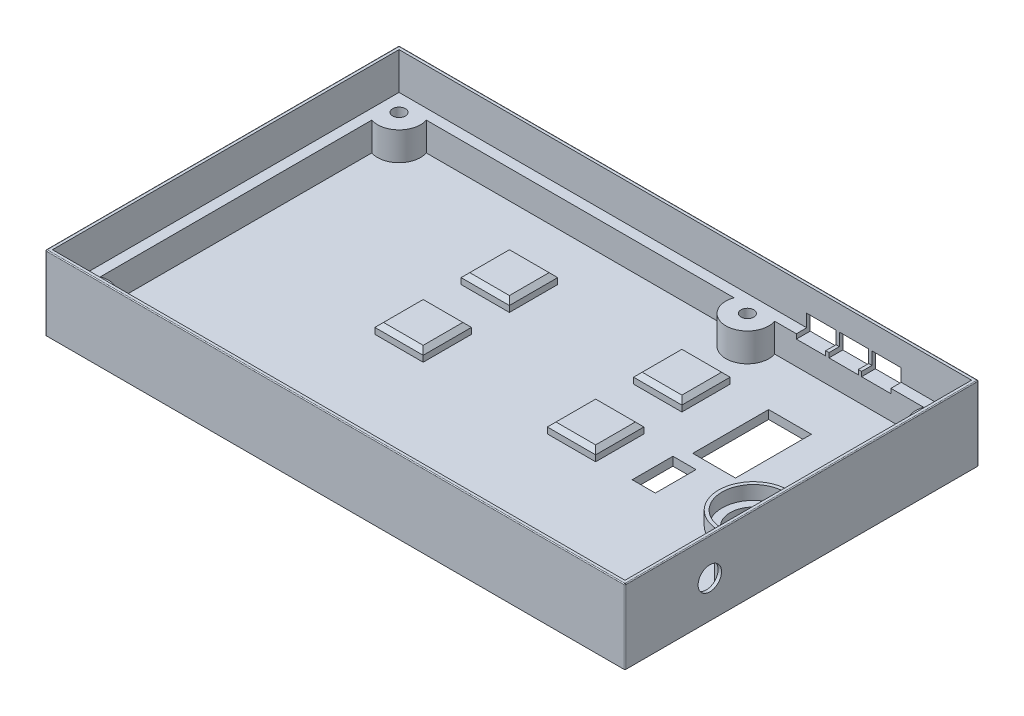
SolidWorks part; units mm, degrees
ref_plane "Front Plane" through (0, 0, 0) normal (0, 0, 1) x (1, 0, 0)
ref_plane "Top Plane" through (0, 0, 0) normal (0, 1, 0) x (1, 0, 0)
ref_plane "Right Plane" through (0, 0, 0) normal (1, 0, 0) x (0, 0, -1)
sketch "BaseSketch1" plane through (0, 0, 0) normal (0, 1, 0) x (1, 0, 0)
  line L1 (0, 0) -> (168, 0)
  line L2 (0, 0) -> (0, 102.5)
  line L3 (0, 102.5) -> (168, 102.5)
  line L4 (168, 0) -> (168, 102.5)
  line L5 (125.95, 83.7) -> (138.35, 83.7)
  line L6 (125.95, 83.7) -> (125.95, 61.7)
  line L7 (125.95, 61.7) -> (138.35, 61.7)
  line L8 (138.35, 83.7) -> (138.35, 61.7)
  line L9 (123.8, 46.3) -> (130.5, 46.3)
  line L10 (123.8, 46.3) -> (123.8, 58.1)
  line L11 (123.8, 58.1) -> (130.5, 58.1)
  line L12 (130.5, 46.3) -> (130.5, 58.1)
  circle A0 centre (57, 77.5) radius 2
  circle A1 centre (107, 77.5) radius 2
  circle A2 centre (57, 52.5) radius 2
  circle A3 centre (107, 52.5) radius 2
  circle A4 centre (6, 96.5) radius 1.85
  circle A5 centre (6, 6) radius 1.85
  circle A6 centre (162, 6) radius 1.85
  circle A7 centre (162, 96.5) radius 1.85
  circle A8 centre (107, 96.5) radius 1.85
  dimension "D16" = 3.7
  dimension "D7" = 4
  dimension "D1" = 102.5
  dimension "D2" = 168
  dimension "D3" = 50
  dimension "D4" = 25
  dimension "D6" = 25
  dimension "D8" = 22
  dimension "D9" = 12.4
  dimension "D10" = 40.8
  dimension "D12" = 6.7
  dimension "D13" = 11.8
  dimension "D15" = 56.2
  dimension "D17" = 6
  dimension "D18" = 6
  dimension "D19" = 6
  dimension "D20" = 6
  dimension "D5" = 57
  dimension "D11" = 42.05
  dimension "D14" = 44.2
  dimension "D21" = 107
extrude "BaseBoss-Extrude1" add sketch "BaseSketch1" along normal blind 2.5
sketch "Sketch2" plane through (0, 2.5, 0) normal (0, 1, 0) x (1, 0, 0)
  line L1 (0, 0) -> (168, 0)
  line L2 (0, 0) -> (0, 102.5)
  line L3 (0, 102.5) -> (168, 102.5)
  line L4 (168, 0) -> (168, 102.5)
  line L5 (4, 98.5) -> (164, 98.5)
  line L6 (4, 98.5) -> (4, 4)
  line L7 (4, 4) -> (164, 4)
  line L8 (164, 98.5) -> (164, 4)
  dimension "D1" = 4
  dimension "D2" = 4
  dimension "D3" = 4
  dimension "D4" = 4
extrude "WallBoss-Extrude2" add sketch "Sketch2" along normal blind 19
sketch "Sketch3" plane through (0, 2.5, 0) normal (0, 1, 0) x (1, 0, 0)
  line L1 (50, 84.5) -> (64, 84.5)
  line L2 (50, 84.5) -> (50, 70.5)
  line L3 (50, 70.5) -> (64, 70.5)
  line L4 (64, 84.5) -> (64, 70.5)
  line L5 (50, 84.5) -> (64, 70.5) construction
  line L6 (50, 70.5) -> (64, 84.5) construction
  line L7 (50, 59.5) -> (64, 59.5)
  line L8 (50, 59.5) -> (50, 45.5)
  line L9 (50, 45.5) -> (64, 45.5)
  line L10 (64, 59.5) -> (64, 45.5)
  line L11 (50, 59.5) -> (64, 45.5) construction
  line L12 (50, 45.5) -> (64, 59.5) construction
  line L13 (100, 84.5) -> (114, 84.5)
  line L14 (100, 84.5) -> (100, 70.5)
  line L15 (100, 70.5) -> (114, 70.5)
  line L16 (114, 84.5) -> (114, 70.5)
  line L17 (100, 84.5) -> (114, 70.5) construction
  line L18 (100, 70.5) -> (114, 84.5) construction
  line L19 (100, 59.5) -> (114, 59.5)
  line L20 (100, 59.5) -> (100, 45.5)
  line L21 (100, 45.5) -> (114, 45.5)
  line L22 (114, 59.5) -> (114, 45.5)
  line L23 (100, 59.5) -> (114, 45.5) construction
  line L24 (100, 45.5) -> (114, 59.5) construction
  point P0 (57, 77.5)
  point P6 (57, 52.5)
  point P12 (107, 77.5)
  point P18 (107, 52.5)
  dimension "D1" = 14
extrude "MountHoleBoss-Extrude3" add sketch "Sketch3" along normal blind 3
chamfer "MountHoleBossChamfer3" distance 1.25 angle 45 16 edges at (57, 5.5, -59.5) (107, 5.5, -59.5) (107, 5.5, -84.5) (57, 5.5, -84.5) (50, 5.5, -52.5) (100, 5.5, -52.5) (100, 5.5, -77.5) (50, 5.5, -77.5) (64, 5.5, -52.5) (114, 5.5, -52.5) (114, 5.5, -77.5) (64, 5.5, -77.5) (57, 5.5, -70.5) (57, 5.5, -45.5) (107, 5.5, -45.5) (107, 5.5, -70.5)
sketch "HDMI7MountHolesSketch8" plane through (0, 2.5, 0) normal (0, 1, 0) x (1, 0, 0)
  line L0 (164, 98.5) -> (4, 98.5) construction
  line L1 (4, 98.5) -> (4, 4) construction
  line L2 (4, 90.5986) -> (4, 98.5)
  line L3 (4, 98.5) -> (11.9014, 98.5)
  line L4 (164, 4) -> (164, 98.5) construction
  line L5 (4, 4) -> (164, 4) construction
  line L6 (4, 98.5) -> (4, 4) construction
  line L7 (4, 4) -> (164, 4) construction
  line L8 (156.0986, 98.5) -> (164, 98.5)
  line L9 (164, 98.5) -> (164, 90.5986)
  line L10 (156.0986, 4) -> (164, 4)
  line L11 (164, 4) -> (164, 11.9014)
  line L12 (11.9014, 4) -> (4, 4)
  line L13 (4, 4) -> (4, 11.9014)
  line L14 (101.0986, 98.5) -> (112.9014, 98.5)
  arc A0 (11.9014, 98.5) -> (4, 90.5986) centre (6, 96.5) cw
  circle A1 centre (6, 96.5) radius 1.85
  circle A2 centre (6, 96.5) radius 1.85 construction
  circle A3 centre (162, 96.5) radius 1.85
  circle A4 centre (162, 96.5) radius 1.85 construction
  arc A5 (164, 90.5986) -> (156.0986, 98.5) centre (162, 96.5) cw
  arc A6 (164, 11.9014) -> (156.0986, 4) centre (162, 6) ccw
  arc A7 (4, 11.9014) -> (11.9014, 4) centre (6, 6) cw
  circle A8 centre (162, 6) radius 1.85
  circle A9 centre (162, 6) radius 1.85 construction
  circle A10 centre (6, 6) radius 1.85
  circle A11 centre (6, 6) radius 1.85 construction
  arc A12 (101.0986, 98.5) -> (112.9014, 98.5) centre (107, 96.5) ccw
  circle A13 centre (107, 96.5) radius 1.85
  circle A14 centre (107, 96.5) radius 1.85 construction
extrude "HDMI7MountHolesBoss-Extrude4" add sketch "HDMI7MountHolesSketch8" along normal blind 8.25
sketch "DisplayButtonsSketch9" plane through (0, 0, -102.5) normal (0, 0, -1) x (-1, 0, 0)
  line L0 (-168, 21.5) -> (0, 21.5) construction
  line L1 (-146.6, 14.41) -> (-138.1, 14.41)
  line L2 (-146.6, 14.41) -> (-146.6, 9.41)
  line L3 (-146.6, 9.41) -> (-138.1, 9.41)
  line L4 (-138.1, 14.41) -> (-138.1, 9.41)
  line L5 (-137.15, 14.41) -> (-128.65, 14.41)
  line L6 (-137.15, 14.41) -> (-137.15, 9.41)
  line L7 (-137.15, 9.41) -> (-128.65, 9.41)
  line L8 (-128.65, 14.41) -> (-128.65, 9.41)
  line L9 (-127.7, 14.41) -> (-119.2, 14.41)
  line L10 (-127.7, 14.41) -> (-127.7, 9.41)
  line L11 (-127.7, 9.41) -> (-119.2, 9.41)
  line L12 (-119.2, 14.41) -> (-119.2, 9.41)
  line L13 (-168, 21.5) -> (-168, 0) construction
  dimension "D1" = 8.5
  dimension "D3" = 12.09
  dimension "D4" = 29.9
  dimension "D2" = 5
  dimension "D6" = 0.95
  dimension "D5" = 0.95
  dimension "D7" = 48.8
  dimension "D8" = 8.5
  dimension "D9" = 8.5
extrude "DisplayButtonsCut-Extrude1" cut sketch "DisplayButtonsSketch9" against normal up to next
sketch "AudioConnectorSketch10" plane through (168, 0, 0) normal (1, 0, 0) x (0, 0, -1)
  line L0 (0, 21.5) -> (102.5, 21.5) construction
  line L1 (0, 21.5) -> (0, 0) construction
  circle A0 centre (24.6, 10.7) radius 3.4
  dimension "D1" = 6.8
  dimension "D2" = 10.8
  dimension "D3" = 24.6
extrude "AudioConnectorCut-Extrude2" cut sketch "AudioConnectorSketch10" against normal up to next
sketch "M3BoreSketch11" plane through (0, 0, 0) normal (0, -1, 0) x (1, 0, 0)
  circle A0 centre (6, -6) radius 2.85
  circle A1 centre (162, -6) radius 2.85
  circle A2 centre (162, -96.5) radius 2.85
  circle A3 centre (6, -96.5) radius 2.85
  circle A4 centre (107, -96.5) radius 2.85
  dimension "D1" = 5.7
extrude "M3BoreCut-Extrude3" cut sketch "M3BoreSketch11" against normal blind 3
sketch "UpperThinWallSketch4" plane through (0, 21.5, 0) normal (0, 1, 0) x (1, 0, 0)
  line L1 (4, 98.5) -> (164, 98.5)
  line L2 (4, 98.5) -> (4, 4)
  line L3 (4, 4) -> (164, 4)
  line L4 (164, 98.5) -> (164, 4)
  line L6 (167, 1) -> (1, 1)
  line L7 (167, 1) -> (167, 101.5)
  line L8 (167, 101.5) -> (1, 101.5)
  line L9 (1, 1) -> (1, 101.5)
  dimension "D1" = 3
  dimension "D2" = 3
  dimension "D3" = 3
  dimension "D4" = 3
extrude "UpperThinWallCut-Extrude1" cut sketch "UpperThinWallSketch4" against normal blind 10.75
sketch "HDMI7AudioConnectorKnotchSketch5" plane through (0, 10.75, 0) normal (0, 1, 0) x (1, 0, 0)
  line L0 (164, 27.9996) -> (167, 27.9996) construction
  line L1 (164, 29.9996) -> (167, 29.9996)
  line L2 (164, 29.9996) -> (164, 19.2004)
  line L3 (164, 19.2004) -> (167, 19.2004)
  line L4 (167, 29.9996) -> (167, 19.2004)
  line L6 (167, 1) -> (167, 21.2004) construction
  line L7 (164, 11.9014) -> (164, 90.5986) construction
  line L8 (167, 21.2004) -> (164, 21.2004) construction
  dimension "D1" = 2
  dimension "D2" = 2
extrude "HDMI7AudioConnectorKnotchCut-Extrude2" cut sketch "HDMI7AudioConnectorKnotchSketch5" against normal blind 8.8
fillet "TopFillet1" radius 0.25 4 edges at (168, 21.5, -51.25) (84, 21.5, 0) (0, 21.5, -51.25) (84, 21.5, -102.5)
fillet "CornerFillet2" radius 0.25 8 edges at (0.0732, 21.4268, -0.0732) (0.0732, 21.4268, -102.4268) (167.9268, 21.4268, -0.0732) (0, 10.625, 0) (0, 10.625, -102.5) (168, 10.625, 0) (167.9268, 21.4268, -102.4268) (168, 10.625, -102.5)
sketch "SpeakerHoleSketch4" plane through (0, 2.5, 0) normal (0, 1, 0) x (1, 0, 0)
  line L0 (0.25, 102.5) -> (167.75, 102.5) construction
  line L1 (168, 102.25) -> (168, 0.25) construction
  circle A0 centre (153, 52.25) radius 6.75
  dimension "D1" = 13.5
  dimension "D2" = 50.25
  dimension "D3" = 15
extrude "SpeaerHoleCut-Extrude1" cut sketch "SpeakerHoleSketch4" against normal through all
sketch "SpeakerHolderSketch5" plane through (0, 2.5, 0) normal (0, 1, 0) x (1, 0, 0)
  line L2 (50, 59.5) -> (50, 45.5) construction
  line L3 (50, 45.5) -> (64, 45.5) construction
  circle A0 centre (153, 52.25) radius 9.1
  circle A1 centre (153, 52.25) radius 10.1
  dimension "D1" = 18.2
  dimension "D2" = 20.2
extrude "SpeakerHolderBoss-Extrude1" add sketch "SpeakerHolderSketch5" along normal blind 4
equation "\"HDMI7CaseWidth\"= 100mm + .5mm'Spec Add .5mm as width was slightly to tight"
equation "\"D1@BaseSketch1\" = \"HDMI7CaseWidth\" + \"HDMI7OuterCaseWallThickness\" * 2"
equation "\"HDMI7CaseLength\"= 165mm + 1mm'Spec Add 1mm as length did not fit"
equation "\"HDMI7CaseHeight\"= 21.5mm"
equation "\"HDMI7Height\"= 10.75mm'Spec"
equation "\"HDMI7MountingHoleOffset\"= 5mm'Spec"
equation "\"M3ScrewDiameter\"= 3mm + .5'Spec Add .5mm for easy screw insert"
equation "\"D2@BaseSketch1\"= \"HDMI7CaseLength\" + \"HDMI7OuterCaseWallThickness\" * 2"
equation "\"HDMI7BaseThickness\"= 2.5mm"
equation "\"HDMIMountHoleXDistance\"=50"
equation "\"D3@BaseSketch1\"=\"HDMIMountHoleXDistance\""
equation "\"HDMIMountHoleYDistance\"=25"
equation "\"D10@BaseSketch1\"=\"HDMI7HDMIConnectorDistanceFromTop\" + \"HDMI7OuterCaseWallThickness\" + \"HDMI7SpaceAroundAConnector\""
equation "\"D6@BaseSketch1\" = \"HDMI7MountingBracketOffsetFromTop\" + \"HDMI7OuterCaseWallThickness\""
equation "\"D15@BaseSketch1\"=\"HDMI7USBCConnectorDistanceFromTop\" + \"HDMI7OuterCaseWallThickness\" + \"HDMI7SpaceAroundAConnector\"*2"
equation "\"D1@BaseBoss-Extrude1\" = \"HDMI7BaseThickness\""
equation "\"D1@Sketch2\"=\"HDMI7OuterCaseWallThickness\" + \"HDMI7InnerCaseWallThickness\""
equation "\"D2@Sketch2\"=\"HDMI7OuterCaseWallThickness\" + \"HDMI7InnerCaseWallThickness\""
equation "\"D3@Sketch2\"=\"HDMI7OuterCaseWallThickness\" +\"HDMI7InnerCaseWallThickness\""
equation "\"D4@Sketch2\"=\"HDMI7OuterCaseWallThickness\" + \"HDMI7InnerCaseWallThickness\""
equation "\"D1@WallBoss-Extrude2\" = \"HDMI7CaseHeight\" - \"HDMI7BaseThickness\""
equation "\"D1@Sketch3\"=\"M3ScrewDiameter\"*4"
equation "\"D1@MountHoleBoss-Extrude3\"=\"M3ButtonHeadLength\""
equation "\"D16@BaseSketch1\"=\"M3ScrewDiameter\" +.2"
equation "\"D18@BaseSketch1\"=\"HDMI7MountingHoleOffset\" + \"HDMI7OuterCaseWallThickness\""
equation "\"D17@BaseSketch1\"=\"HDMI7MountingHoleOffset\"+\"HDMI7OuterCaseWallThickness\""
equation "\"D19@BaseSketch1\"=\"HDMI7MountingHoleOffset\"+\"HDMI7OuterCaseWallThickness\""
equation "\"D20@BaseSketch1\"=\"HDMI7MountingHoleOffset\"+\"HDMI7OuterCaseWallThickness\""
equation "\"D1@HDMI7MountHolesBoss-Extrude4\"=\"HDMI7CaseHeight\" - \"HDMI7Height\" - \"HDMI7BaseThickness\""
equation "\"D5@BaseSketch1\" = \"HDMI7MountingBracketOffsetFromEdge\" + \"HDMI7OuterCaseWallThickness\""
equation "\"D4@DisplayButtonsSketch9\"=\"HDMI7DisplayButtonDistanceFromNearestEdge\" + \"HDMI7OuterCaseWallThickness\" + \"HDMI7SpaceAroundAConnector\""
equation "\"D2@AudioConnectorSketch10\"= \"HDMI7AudioConnectorDistanceFromTop\" - \"HDMI7AudioConnectorHoleDiameter\" / 2"
equation "\"D3@AudioConnectorSketch10\"= \"HDMI7AudioConnectorDistanceFromNearestEdge\" + \"HDMI7OuterCaseWallThickness\" - \"HDMI7AudioConnectorHoleDiameter\" / 2"
equation "\"M3ButtonHeadDiameter\"= 5.5mm'Spec"
equation "\"M3ButtonHeadLength\"= 3mm'Spec"
equation "\"D1@M3BoreSketch11\"=\"M3ButtonHeadDiameter\" + .2mm"
equation "\"D1@M3BoreCut-Extrude3\"=\"M3ButtonHeadLength\""
equation "\"HDMI7InnerCaseWallThickness\"= 3mm"
equation "\"HDMI7OuterCaseWallThickness\"= 1mm"
equation "\"D1@UpperThinWallSketch4\" = \"HDMI7InnerCaseWallThickness\""
equation "\"D2@UpperThinWallSketch4\" = \"HDMI7InnerCaseWallThickness\""
equation "\"D3@UpperThinWallSketch4\" = \"HDMI7InnerCaseWallThickness\""
equation "\"D4@UpperThinWallSketch4\" = \"HDMI7InnerCaseWallThickness\""
equation "\"D1@UpperThinWallCut-Extrude1\" = \"HDMI7Height\""
equation "\"HDMI7AudioConnectorHoleDiameter\"= 6mm + \"HDMI7SpaceAroundAConnector\" * 2"
equation "\"D1@AudioConnectorSketch10\"=\"HDMI7AudioConnectorHoleDiameter\""
equation "\"HDMI7AudioConnectorDistanceFromNearestEdge\"= 27mm"
equation "\"HDMI7AudioConnectorDistanceFromTop\"= 13.8mm + \"HDMI7SpaceAroundAConnector\""
equation "\"D1@HDMI7AudioConnectorKnotchCut-Extrude2\"=\"HDMI7AudioConnectorHoleDiameter\" + 2mm"
equation "\"HDMI7DisplayButtonDistanceFromTop\"=11.69"
equation "\"D3@DisplayButtonsSketch9\"=\"HDMI7DisplayButtonDistanceFromTop\" + \"HDMI7SpaceAroundAConnector\""
equation "\"HDMI7DisplayButtonHeight\"= 4.2mm"
equation "\"D2@DisplayButtonsSketch9\"=\"HDMI7DisplayButtonHeight\" + \"HDMI7SpaceAroundAConnector\"*2"
equation "\"HDMI7DisplayButtonWidth\"= 7.7mm"
equation "\"D1@DisplayButtonsSketch9\"=\"HDMI7DisplayButtonWidth\" + \"HDMI7SpaceAroundAConnector\" * 2"
equation "\"HDMI7DisplayButtonDistanceFromNearestEdge\"= 28.5mm"
equation "\"HDMI7DisplayButtonOffsetBetweenEach\"=1.75"
equation "\"D6@DisplayButtonsSketch9\"=\"HDMI7DisplayButtonOffsetBetweenEach\" - \"HDMI7SpaceAroundAConnector\"*2"
equation "\"D5@DisplayButtonsSketch9\"=\"HDMI7DisplayButtonOffsetBetweenEach\" - \"HDMI7SpaceAroundAConnector\"*2"
equation "\"HDMI7HDMIConnectorLength\"= 21.2mm"
equation "\"D8@BaseSketch1\"=\"HDMI7HDMIConnectorLength\" + \"HDMI7SpaceAroundAConnector\"*2"
equation "\"HDMI7HDMIConnectorWidth\"= 11.6mm"
equation "\"D9@BaseSketch1\"=\"HDMI7HDMIConnectorWidth\" + \"HDMI7SpaceAroundAConnector\"*2"
equation "\"HDMI7USBCConnectorLength\"= 11mm"
equation "\"D13@BaseSketch1\"=\"HDMI7USBCConnectorLength\" + \"HDMI7SpaceAroundAConnector\"*2"
equation "\"HDMI7USBCConnectorWidth\"= 5.9mm'Measured"
equation "\"D12@BaseSketch1\"=\"HDMI7USBCConnectorWidth\" + \"HDMI7SpaceAroundAConnector\"*2"
equation "\"HDMI7HDMIConnectorDistanceFromNearestSide\" = 38.65mm"
equation "\"HDMI7USBCConnectorDistanceFromNearestSide\" = 40.8mm"
equation "\"D11@BaseSketch1\"=\"HDMI7HDMIConnectorDistanceFromNearestSide\" + \"HDMI7InnerCaseWallThickness\" + \"HDMI7SpaceAroundAConnector\""
equation "\"D14@BaseSketch1\"=\"HDMI7USBCConnectorDistanceFromNearestSide\" +\"HDMI7InnerCaseWallThickness\" + \"HDMI7SpaceAroundAConnector\""
equation "\"HDMI7USBCConnectorDistanceFromTop\"= 54.4mm"
equation "\"HDMI7HDMIConnectorDistanceFromTop\"= 39.4mm"
equation "\"HDMI7MountingBracketOffsetFromEdge\"= 56mm"
equation "\"HDMI7MountingBracketOffsetFromTop\"= 24mm"
equation "\"HDMI7SpaceAroundAConnector\" = .4mm"
equation "\"D7@BaseSketch1\"= \"M3HeatInsertHoleDiameter\""
equation "\"D8@DisplayButtonsSketch9\"=\"HDMI7DisplayButtonWidth\" + \"HDMI7SpaceAroundAConnector\"*2"
equation "\"D9@DisplayButtonsSketch9\"=\"HDMI7DisplayButtonWidth\" + \"HDMI7SpaceAroundAConnector\"*2"
equation "\"HDMI7MidMouningHoleOffset\"= 107'Spec is 106.55 but not enough"
equation "\"M3HeatInsertHoleDiameter\"= 4mm'Spec"
equation "\"SpeakerHoleDiameter\"= 13.5mm"
equation "\"D2@SpeakerHoleSketch4\" = \"HDMI7CaseWidth\" / 2"
equation "\"SpeakerDistanceFromNearestEdge\"= 15mm"
equation "\"D3@SpeakerHoleSketch4\" = \"SpeakerDistanceFromNearestEdge\""
equation "\"SpeakerDiameter\"= 18.2mm'Spec Add .2mm for Filament expansion"
equation "\"D1@SpeakerHolderSketch5\"=\"SpeakerDiameter\""
equation "\"D2@SpeakerHolderSketch5\"=\"SpeakerDiameter\" + 2mm"
equation "\"SpeakerDepth\"=4"
equation "\"D1@SpeakerHolderBoss-Extrude1\"=\"SpeakerDepth\""
equation "\"D21@BaseSketch1\"=\"HDMI7MidMouningHoleOffset\""
